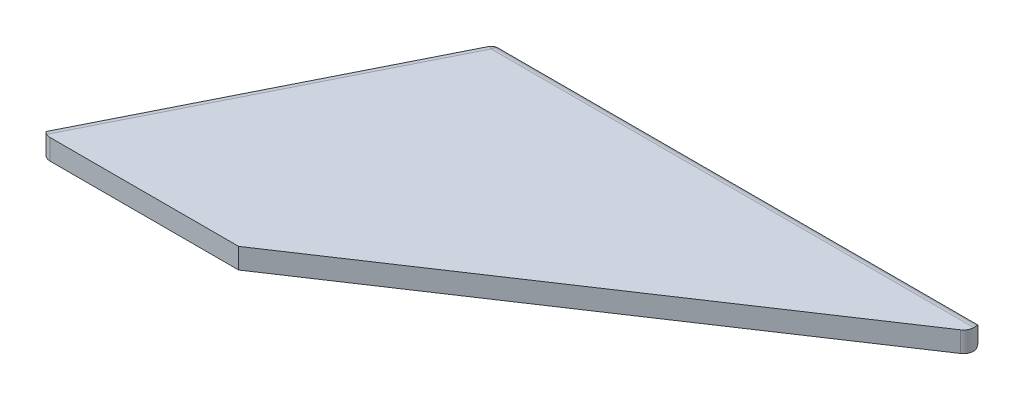
SolidWorks part; units mm, degrees
ref_plane "Front Plane" through (0, 0, 0) normal (0, 0, 1) x (1, 0, 0)
ref_plane "Top Plane" through (0, 0, 0) normal (0, 1, 0) x (1, 0, 0)
ref_plane "Right Plane" through (0, 0, 0) normal (1, 0, 0) x (0, 0, -1)
sketch "Sketch1" plane through (0, 0, 0) normal (0, 1, 0) x (1, 0, 0)
  line L0 (0, 0) -> (-20, 0)
  line L1 (-20, 0) -> (-4.9771, 30)
  line L2 (-4.9771, 30) -> (45.0229, 30)
  line L3 (45.0229, 30) -> (0, 0)
  dimension "D1" = 20
  dimension "D2" = 50
  dimension "D3" = 30
  dimension "D4" = 63.4
extrude "Boss-Extrude1" add sketch "Sketch1" along normal blind 2
fillet "Fillet2" radius 1 6 edges at (45.0229, 1, -30) (20.0229, 2, -30) (20.0229, 0, -30) (-12.4886, 2, -15) (-20, 1, 0) (-12.4886, 0, -15)
